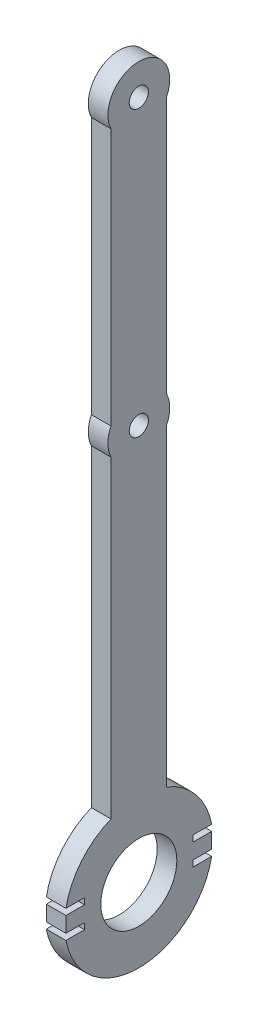
SolidWorks part; units mm, degrees
ref_plane "Front Plane" through (0, 0, 0) normal (0, 0, 1) x (1, 0, 0)
ref_plane "Top Plane" through (0, 0, 0) normal (0, 1, 0) x (1, 0, 0)
ref_plane "Right Plane" through (0, 0, 0) normal (1, 0, 0) x (0, 0, -1)
sketch "Sketch1" plane through (0, 0, 0) normal (1, 0, 0) x (0, 0, -1)
  line L0 (0, 0) -> (-4.5, -2.1794) construction
  line L2 (4.5, -2.1794) -> (4.5, -43.8206)
  line L3 (4.5, -43.8206) -> (-4.5, -43.8206) construction
  line L4 (-4.5, -2.1794) -> (-4.5, -43.8206)
  line L5 (4.5, -2.1794) -> (-4.5, -2.1794) construction
  line L6 (0, 0) -> (4.5, -2.1794) construction
  line L8 (-4.5, -48.1794) -> (-4.5, -98.8757)
  line L9 (4.5, -48.1794) -> (4.5, -98.8757)
  line L11 (0, -46) -> (0, -110) construction
  line L12 (8.7872, -111.25) -> (8.7872, -112.25)
  line L13 (-4.5, -48.1794) -> (4.5, -48.1794) construction
  line L14 (8.7872, -107.75) -> (11.7872, -107.75)
  line L15 (8.7872, -107.75) -> (8.7872, -108.75)
  line L16 (8.7872, -112.25) -> (11.7872, -112.25)
  line L18 (8.7872, -108.75) -> (11.7872, -108.75)
  line L20 (8.7872, -111.25) -> (11.7872, -111.25)
  line L21 (11.7872, -108.75) -> (11.7872, -111.25)
  line L22 (-11.7872, -108.75) -> (-11.7872, -111.25)
  line L23 (-8.7872, -111.25) -> (-11.7872, -111.25)
  line L24 (-8.7872, -108.75) -> (-11.7872, -108.75)
  line L25 (-8.7872, -112.25) -> (-11.7872, -112.25)
  line L26 (-8.7872, -107.75) -> (-8.7872, -108.75)
  line L27 (-8.7872, -107.75) -> (-11.7872, -107.75)
  line L28 (-8.7872, -111.25) -> (-8.7872, -112.25)
  circle A0 centre (0, 0) radius 1.55
  arc A1 (4.5, -2.1794) -> (-4.5, -2.1794) centre (0, 0) ccw
  arc A2 (-4.5, -43.8206) -> (-4.5, -48.1794) centre (0, -46) ccw
  circle A3 centre (0, -46) radius 1.55
  arc A4 (-4.5, -98.8757) -> (-11.7872, -107.75) centre (0, -110) ccw
  circle A5 centre (0, -110) radius 6.15
  arc A6 (4.5, -48.1794) -> (4.5, -43.8206) centre (0, -46) ccw
  arc A7 (11.7872, -107.75) -> (4.5, -98.8757) centre (0, -110) ccw
  arc A8 (-11.7872, -112.25) -> (11.7872, -112.25) centre (0, -110) ccw
  point P20 (11.7872, -110)
  point P36 (-11.7872, -110)
  dimension "D1" = 3.1
  dimension "D2" = 10
  dimension "D4" = 10
  dimension "D6" = 3.1
  dimension "D10" = 12.3
  dimension "D9" = 12
  dimension "D3" = 9
  dimension "D5" = 46
  dimension "D7" = 9
  dimension "D8" = 64
  dimension "D11" = 3
  dimension "D12" = 2.5
  dimension "D13" = 1
extrude "Boss-Extrude3" add sketch "Sketch1" along normal blind 3.175
equation "\"D3@Sketch1\"=\"D7@Sketch1\""
